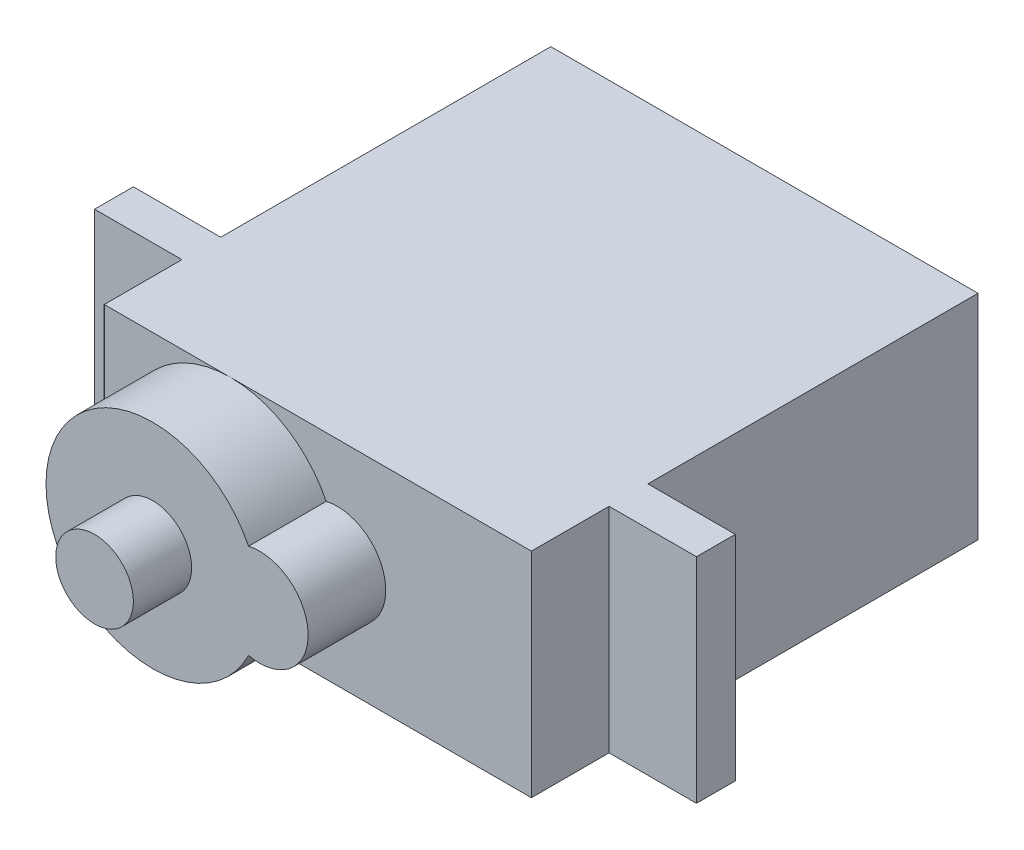
SolidWorks part; units mm, degrees
ref_plane "Front Plane" through (0, 0, 0) normal (0, 0, 1) x (1, 0, 0)
ref_plane "Top Plane" through (0, 0, 0) normal (0, 1, 0) x (1, 0, 0)
ref_plane "Right Plane" through (0, 0, 0) normal (1, 0, 0) x (0, 0, -1)
sketch "Sketch2" plane through (0, 0, 0) normal (0, 0, 1) x (1, 0, 0)
  line L0 (-15.5, 0) -> (15.5, 0) construction
  line L1 (-15.5, 5.5) -> (15.5, 5.5)
  line L2 (-15.5, 5.5) -> (-15.5, -5.5)
  line L3 (-15.5, -5.5) -> (15.5, -5.5)
  line L4 (15.5, 5.5) -> (15.5, -5.5)
  line L5 (-15.5, 5.5) -> (15.5, -5.5) construction
  line L6 (-15.5, -5.5) -> (15.5, 5.5) construction
  circle A0 centre (-4.5, 0) radius 2
  point P0 (0, 0)
  dimension "D3" = 4
  dimension "D1" = 31
  dimension "D2" = 11
  dimension "D4" = 11
extrude "Boss-Extrude1" add sketch "Sketch2" along normal blind 23
extrude "Boss-Extrude2" add sketch "Sketch2<2>" along normal blind 30 contours A0 region at (-4.5, 0, 0)
sketch "Sketch2<2>" plane through (0, 0, 0) normal (0, 0, 1) x (1, 0, 0) same geometry as "Sketch2"
sketch "Sketch3" plane through (0, 0, 23) normal (0, 0, 1) x (1, 0, 0)
  line L0 (-15.5, -5.5) -> (15.5, -5.5) construction
  line L1 (-11, 5.5) -> (11, 5.5)
  line L2 (-11, 5.5) -> (-11, -5.5)
  line L3 (-11, -5.5) -> (11, -5.5)
  line L4 (11, 5.5) -> (11, -5.5)
  line L5 (-11, 5.5) -> (11, -5.5) construction
  line L6 (-11, -5.5) -> (11, 5.5) construction
  line L8 (-11, 5.5) -> (-15.5, 5.5)
  line L9 (-11, 5.5) -> (-11, -5.5)
  line L10 (-11, -5.5) -> (-15.5, -5.5)
  line L11 (-15.5, 5.5) -> (-15.5, -5.5)
  line L12 (11, 5.5) -> (15.5, 5.5)
  line L13 (11, 5.5) -> (11, -5.5)
  line L14 (11, -5.5) -> (15.5, -5.5)
  line L15 (15.5, 5.5) -> (15.5, -5.5)
  point P0 (0, 0)
  line M2 (15.5, -5.5) -> (15.5, 5.5)
  line M3 (15.5, 5.5) -> (-15.5, 5.5)
  line M4 (-15.5, 5.5) -> (-15.5, -5.5)
  line M5 (-15.5, -5.5) -> (15.5, -5.5)
  dimension "D1" = 22
extrude "Cut-Extrude1" cut sketch "Sketch3" against normal blind 4 contours L2 M3 M4 M5 | L4 M3 M5 M2 region at (-13.25, 0, 23) region at (13.25, 0, 23)
extrude "Cut-Extrude2" cut sketch "Sketch3<5>" against normal through all from offset 6 contours L2 M3 M4 M5 | L4 M3 M5 M2 region at (-13.25, 0, 23) region at (13.25, 0, 23) offset against normal yes
sketch "Sketch3<5>" plane through (0, 0, 23) normal (0, 0, 1) x (1, 0, 0) same geometry as "Sketch3"
sketch "Sketch4" plane through (0, 0, 23) normal (0, 0, 1) x (1, 0, 0)
  line L0 (-11, 0) -> (11, 0) construction
  line L1 (-11, 5.5) -> (-11, -5.5) construction
  line L2 (11, 5.5) -> (11, -5.5) construction
  circle A0 centre (-4.5, 0) radius 5.5
  arc A1 (0.4318, -2.4346) -> (0.4318, 2.4346) centre (1, 0) ccw
  point P12 (0, 0)
  circle M1 centre (-4.5, 0) radius 2
  dimension "D1" = 11
  dimension "D2" = 5
  dimension "D3" = 12
extrude "Boss-Extrude3" add sketch "Sketch4" along normal blind 4 contours A0 L0 M1 | L0 A0 M1 | L0 M1 | L0 M1 | L0 A0 A1 | A0 L0 A1 region at (-4.5, 2.5606, 23) region at (-4.5, -0.8488, 23) region at (-4.5, 0.8488, 23) region at (-4.5, -2.5606, 23) region at (1.9521, 1.1321, 23) region at (1.9521, -1.1321, 23)
